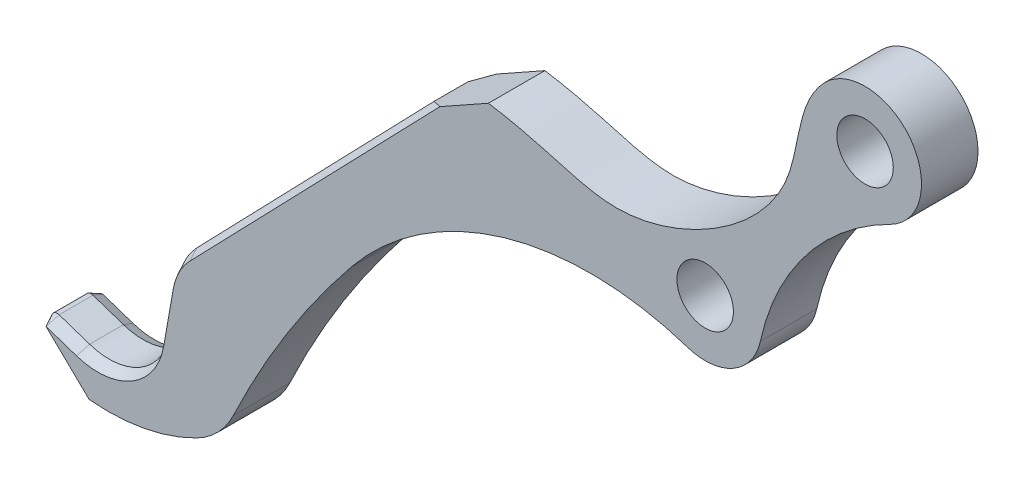
SolidWorks part; units mm, degrees
ref_plane "前基準面" through (0, 0, 0) normal (0, 0, 1) x (1, 0, 0)
ref_plane "上基準面" through (0, 0, 0) normal (0, 1, 0) x (1, 0, 0)
ref_plane "右基準面" through (0, 0, 0) normal (1, 0, 0) x (0, 0, -1)
sketch "草圖1" plane through (0, 0, 0) normal (0, 0, 1) x (1, 0, 0)
  line L0 (0, 0) -> (35.657, 18.1268) construction
  line L1 (35.657, 18.1268) -> (21.5, 0) construction
  line L2 (21.5, 0) -> (0, 0) construction
  line L3 (33.2106, 22.4874) -> (9.2127, 9.0241)
  line L4 (9.2127, -5) -> (21.5, -5)
  line L5 (25.4406, -3.0776) -> (39.5976, 15.0492)
  line L6 (9.2127, -5) -> (9.2127, -41.3862)
  line L11 (9.2127, 13.2175) -> (-51.0185, 13.2175)
  line L12 (9.2127, 13.2175) -> (9.2127, 9.0241)
  line L13 (9.2127, -41.3862) -> (-51.0185, -41.3862)
  line L14 (-51.0185, 13.2175) -> (-51.0185, -41.3862)
  circle A0 centre (0, 0) radius 2.5 construction
  circle A1 centre (21.5, 0) radius 2.5
  circle A2 centre (35.657, 18.1268) radius 2.5
  arc A4 (39.5976, 15.0492) -> (33.2106, 22.4874) centre (35.657, 18.1268) ccw
  arc A5 (21.5, -5) -> (25.4406, -3.0776) centre (21.5, 0) ccw
  circle A7 centre (21.5, 0) radius 5 construction
  circle A8 centre (35.657, 18.1268) radius 5 construction
  dimension "D4" = 5
  dimension "D1" = 40
  dimension "D2" = 23
  dimension "D3" = 21.5
  dimension "D5" = 2.5
extrude "填料-伸長1" add sketch "草圖1" along normal mid plane 5
sketch "草圖2" plane through (0, 0, 2.5) normal (0, 0, 1) x (1, 0, 0)
  line L0 (33.2106, 22.4874) -> (9.2127, 9.0241) construction
  line L5 (-3.5047, 1.8894) -> (-24.4991, -19.8371)
  line L7 (2.3035, 5.1479) -> (-3.5047, 1.8894)
  line L8 (-27.3354, -29.1023) -> (-32.5461, -32.1174) construction
  line L10 (-34.0049, -31.9849) -> (-36.7073, -31.0767)
  line L12 (-37.214, -31.9102) -> (-33.8756, -35.1362)
  line L16 (-26.9401, -27.7851) -> (-26.0939, -22.9682)
  arc A0 (-26.9401, -27.7851) -> (-34.0049, -31.9849) centre (-32.2784, -26.8472) cw
  arc A1 (21.5, -5) -> (25.4406, -3.0776) centre (21.5, 0) ccw construction
  arc A2 (39.5976, 15.0492) -> (33.2106, 22.4874) centre (35.657, 18.1268) ccw construction
  arc A3 (-26.0939, -22.9682) -> (-24.4991, -19.8371) centre (-20.1844, -24.0064) cw
  arc A4 (19.9292, -4.7469) -> (26.3839, -1.0712) centre (21.5, 0) ccw
  arc A5 (37.8795, 13.6479) -> (32.0722, 21.6124) centre (35.657, 18.1268) ccw
  arc A6 (37.8795, 13.6479) -> (26.3839, -1.0712) centre (47.4798, -5.6985) ccw
  arc A7 (19.9292, -4.7469) -> (-9.8512, -13.4921) centre (11.3597, -30.6434) ccw
  arc A13 (-36.7073, -31.0767) -> (-37.214, -31.9102) centre (-36.8666, -31.5507) ccw
  arc A14 (-9.8512, -13.4921) -> (-20.2786, -30.0889) centre (54.3335, -65.3923) ccw
  arc A15 (-20.2786, -30.0889) -> (-23.5207, -33.4335) centre (-26.8158, -26.9957) cw
  arc A16 (-23.5207, -33.4335) -> (-33.8756, -35.1362) centre (-31.3549, -18.1277) cw
  spline S0 degree 3 poles (32.0722, 21.6124) (29.6196, 19.09) (30.5294, 9.3841) (14.4971, 0.221) (7.8953, 4.291) (2.3035, 5.1479) knots 0 0 0 0 0.241566 0.691253 1 1 1 1
  point P2 (-27.3354, -23.6692)
  point P5 (-27.3437, -23.4494)
  point P7 (-27.3354, -22.8735)
  point P28 (-26.0939, -22.9682)
  dimension "D1" = 6
  dimension "D3" = 0.5
extrude "除料-伸長1" cut sketch "草圖2" against normal blind 5 flip side to cut
chamfer "導角1" distance 1 distance2 0.5 7 edges at (-35.5448, -33.5232, 2.5) (-37.2938, -31.2909, 2.5) (-35.3561, -31.5308, 2.5) (-26.517, -25.3767, 2.5) (-14.0019, -8.9739, 2.5) (-29.5088, -31.5062, 2.5) (-25.5308, -21.2833, 2.5) first distance on face at (-35.5448, -33.5232, 0) first distance on face at (-37.1272, -31.3922, 0) first distance on face at (-35.3561, -31.5308, 0) first distance on face at (-26.517, -25.3767, 0) first distance on face at (-14.0019, -8.9739, 0) first distance on face at (-29.9906, -30.6956, 0) first distance on face at (-25.4137, -21.343, 0)
chamfer "導角2" distance 0.5 distance2 1 7 edges at (-35.5448, -33.5232, -2.5) (-37.2938, -31.2909, -2.5) (-35.3561, -31.5308, -2.5) (-26.517, -25.3767, -2.5) (-14.0019, -8.9739, -2.5) (-29.5088, -31.5062, -2.5) (-25.5308, -21.2833, -2.5) first distance on face at (24, 0, -2.5)
